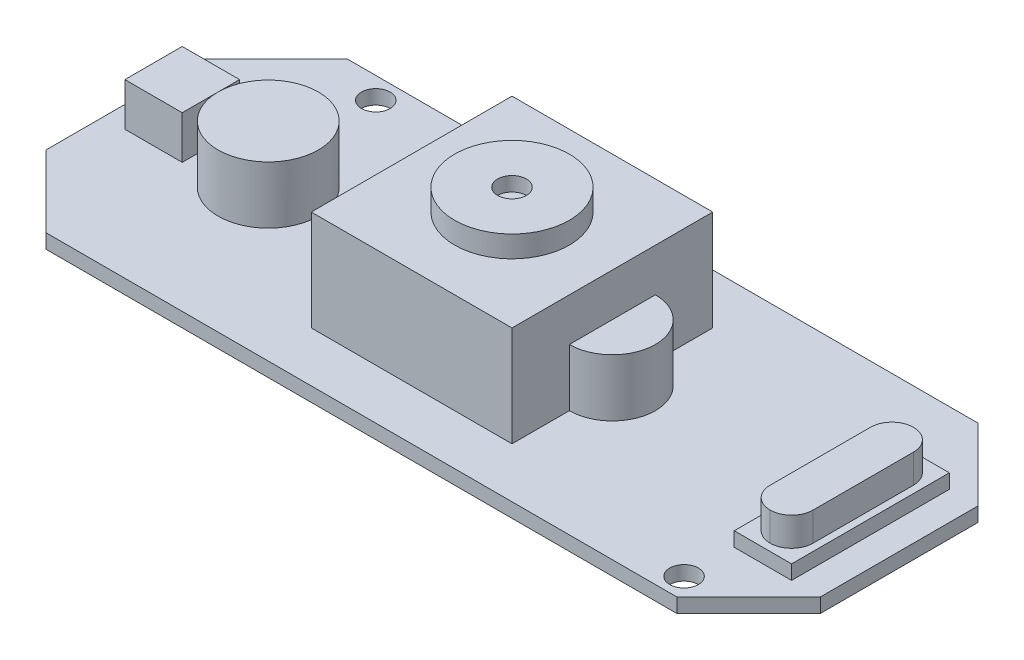
SolidWorks part; units mm, degrees
ref_plane "Front Plane" through (0, 0, 0) normal (0, 0, 1) x (1, 0, 0)
ref_plane "Top Plane" through (0, 0, 0) normal (0, 1, 0) x (1, 0, 0)
ref_plane "Right Plane" through (0, 0, 0) normal (1, 0, 0) x (0, 0, -1)
sketch "Sketch1" plane through (0, 0, 0) normal (0, 1, 0) x (1, 0, 0)
  line L1 (-22, -10.5) -> (22, -10.5)
  line L2 (-27, -5.5) -> (-27, 5.5)
  line L3 (-22, 10.5) -> (22, 10.5)
  line L4 (27, -5.5) -> (27, 5.5)
  line L5 (-27, -10.5) -> (27, 10.5) construction
  line L6 (-27, 10.5) -> (27, -10.5) construction
  line L7 (-22, 10.5) -> (-27, 5.5)
  line L10 (22, 10.5) -> (27, 5.5)
  line L11 (-22, -10.5) -> (-27, -5.5)
  line L12 (22, -10.5) -> (27, -5.5)
  point P0 (0, 0)
  dimension "D1" = 21
  dimension "D2" = 54
  dimension "D3" = 5
  dimension "D4" = 5
extrude "Boss-Extrude1" add sketch "Sketch1" along normal blind 1
sketch "Sketch2" plane through (0, 1, 0) normal (0, 1, 0) x (1, 0, 0)
  line L1 (-7, -7) -> (7, -7)
  line L2 (-7, -7) -> (-7, 7)
  line L3 (-7, 7) -> (7, 7)
  line L4 (7, -7) -> (7, 7)
  line L5 (-7, -7) -> (7, 7) construction
  line L6 (-7, 7) -> (7, -7) construction
  point P0 (0, 0)
  dimension "D1" = 14
  dimension "D2" = 14
extrude "Boss-Extrude2" add sketch "Sketch2" along normal blind 7
sketch "Sketch3" plane through (0, 8, 0) normal (0, 1, 0) x (1, 0, 0)
  circle A0 centre (0, 0) radius 4
extrude "Boss-Extrude3" add sketch "Sketch3" along normal blind 1.5
sketch "Sketch4" plane through (0, 1, 0) normal (0, 1, 0) x (1, 0, 0)
  line L0 (7, -7) -> (7, 7) construction
  line L1 (0, 0) -> (0, 6.3227)
  circle A0 centre (7, 0) radius 3
  circle A1 centre (-7, 0) radius 3
  line M10 (7, 7) -> (7, -7)
  line M12 (-7, -7) -> (-7, 7)
extrude "Boss-Extrude4" add sketch "Sketch4" along normal blind 4 contours A0 M10 | A1 M12 region at (8.2732, 1, 0) region at (-8.2732, 1, 0)
sketch "Sketch6" plane through (0, 9.5, 0) normal (0, 1, 0) x (1, 0, 0)
  circle A0 centre (0, 0) radius 1
extrude "Cut-Extrude1" cut sketch "Sketch6" against normal blind 1
sketch "Sketch7" plane through (0, 1, 0) normal (0, 1, 0) x (1, 0, 0)
  line L0 (-22, 10.5) -> (-18.5, 10.5)
  line L1 (22, 10.5) -> (-22, 10.5) construction
  line L2 (-18.5, 10.5) -> (-18.5, 9)
  line L6 (22, -10.5) -> (22, -9)
  line L7 (22, -9) -> (21, -9)
  circle A0 centre (-18.5, 9) radius 1
  circle A1 centre (21, -9) radius 1
  dimension "D3" = 1
  dimension "D1" = 3.5
  dimension "D2" = 1.5
  dimension "D4" = 1.5
extrude "Cut-Extrude2" cut sketch "Sketch7" against normal up to next contours A1 | A0
sketch "Sketch8" plane through (0, 1, 0) normal (0, 1, 0) x (1, 0, 0)
  line L0 (-27, 0) -> (-17, 0)
  line L1 (-27, 5.5) -> (-27, -5.5) construction
  circle A0 centre (-17, 0) radius 3.5
extrude "Boss-Extrude5" add sketch "Sketch8" along normal blind 4 contours A0 region at (-17, 1, 3.401)
sketch "Sketch9" plane through (0, 1, 0) normal (0, 1, 0) x (1, 0, 0)
  line L0 (-27, 0) -> (-25.5, 0)
  line L1 (-27, 5.5) -> (-27, -5.5) construction
  line L2 (-27, 5.5) -> (-27, 2.5)
  line L3 (-27, 2.5) -> (-25.5, 2.5)
  line L4 (-25.5, 2.5) -> (-21.5, 2.5)
  line L5 (-21.5, 2.5) -> (-21.5, -1.5)
  line L6 (-21.5, -1.5) -> (-25.5, -1.5)
  line L7 (-25.5, -1.5) -> (-25.5, 2.5)
extrude "Boss-Extrude6" add sketch "Sketch9" along normal blind 3 contours L7 L6 L5 L4 region at (-23.5, 1, -0.5)
sketch "Sketch11" plane through (0, 1, 0) normal (0, 1, 0) x (1, 0, 0)
  line L0 (22, -10.5) -> (22, -5.5)
  line L1 (27, -5.5) -> (25, -5.5)
  line L2 (25, -5.5) -> (25, 5.5)
  line L6 (25, 5.5) -> (21, 5.5)
  line L7 (21, 5.5) -> (21, -5.5)
  line L8 (21, -5.5) -> (25, -5.5)
  dimension "D1" = 4
extrude "Boss-Extrude7" add sketch "Sketch11" along normal blind 1 contours L7 L8 L2 L6 region at (23, 1, 0)
sketch "Sketch12" plane through (0, 2, 0) normal (0, 1, 0) x (1, 0, 0)
  line L4 (21.5, 5) -> (24.5, 5)
  line L5 (21.5, 5) -> (21.5, -5)
  line L6 (21.5, -5) -> (24.5, -5)
  line L7 (24.5, 5) -> (24.5, -5)
  line L8 (21.5, 5) -> (24.5, -5) construction
  line L9 (21.5, -5) -> (24.5, 5) construction
  point P6 (23, 0)
  dimension "D1" = 10
  dimension "D2" = 3
extrude "Boss-Extrude8" add sketch "Sketch12" along normal blind 2
fillet "Fillet1" radius 1.5 4 edges at (24.5, 3, -5) (21.5, 3, -5) (21.5, 3, 5) (24.5, 3, 5)
